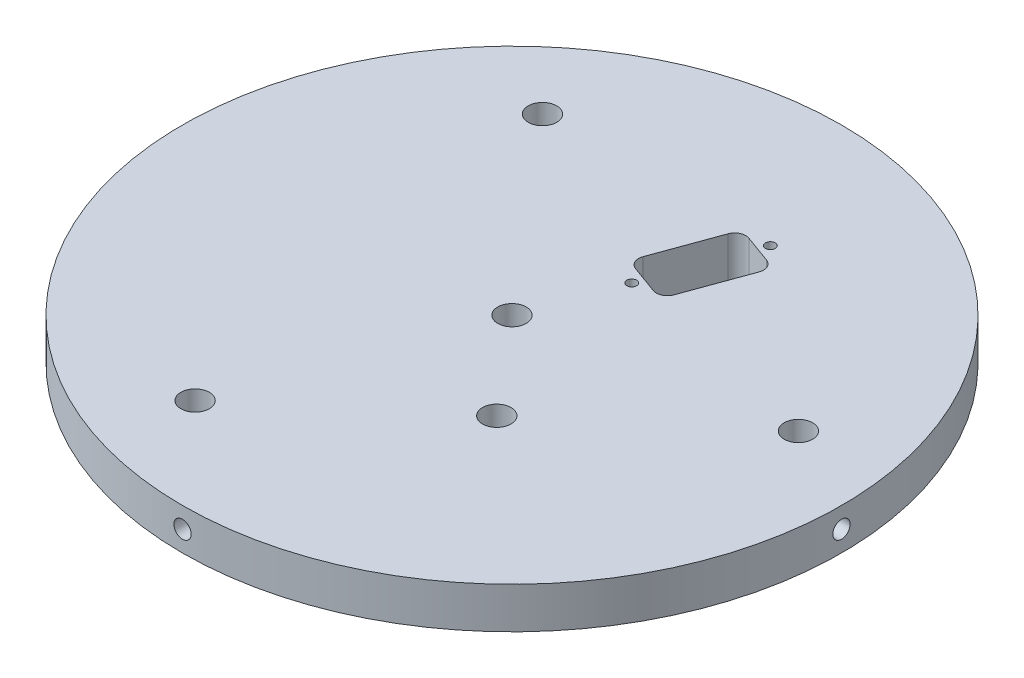
SolidWorks part; units mm, degrees
material "6061-T6 (SS)"
ref_plane "Front Plane" through (0, 0, 0) normal (0, 0, 1) x (1, 0, 0)
ref_plane "Top Plane" through (0, 0, 0) normal (0, 1, 0) x (1, 0, 0)
ref_plane "Right Plane" through (0, 0, 0) normal (1, 0, 0) x (0, 0, -1)
sketch "Sketch1" plane through (0, 0, 0) normal (0, 1, 0) x (1, 0, 0)
  line L0 (0, 0) -> (-50.3682, 60.0265)
  line L1 (0, 0) -> (50.3682, 60.0265)
  line L2 (0, 0) -> (0, 72.1431) construction
  circle A0 centre (0, 0) radius 78.359
  circle A1 centre (0, 0) radius 76.1746
  circle A2 centre (0, 0) radius 76.1746
  dimension "D1" = 156.718
  dimension "D2" = 152.3492
  dimension "D3" = 152.3492
  dimension "D4" = 80
extrude "Boss-Extrude1" add sketch "Sketch1" along normal blind 25.4 contours L2 A2 L1 A0 | L2 A1 L1 A2 | L2 A2 L1 A1 | L2 A0 L1 A2 | A2 L2 A1 L0 | A0 L2 A2 L0 | A2 L2 A0 L0 | A1 L2 A2 L0 region at (0, 0, 13.3592) region at (-23.5316, 0, -29.974) region at (-33.0764, 0, 70.9325) region at (-48.8794, 0, -59.85)
ref_plane "Plane1" through (0, 12.7, 0) normal (0, 1, 0) x (1, 0, 0)
sketch "Sketch6" plane through (0, 25.4, 0) normal (0, 1, 0) x (1, 0, 0)
  circle A0 centre (0, 0) radius 76.1746
  dimension "D1" = 152.3492
extrude "Boss-Extrude5" add sketch "Sketch6" along normal blind 9.525
sketch "Sketch7" plane through (0, 0, 0) normal (0, -1, 0) x (1, 0, 0)
  circle A0 centre (0, 0) radius 76.1746
  dimension "D1" = 152.3492
extrude "Boss-Extrude6" add sketch "Sketch7" along normal blind 9.525
sketch "Sketch8" plane through (0, -9.525, 0) normal (0, -1, 0) x (1, 0, 0)
  circle A0 centre (0, 0) radius 73.025
  dimension "D1" = 146.05
extrude "Cut-Extrude5" cut sketch "Sketch8" against normal up to surface (34.925 mm away) up to face at (0, 25.4, 76.1746)
ref_plane "Plane2" through (0, 0, -76.1746) normal (0, 0, -1) x (-1, 0, 0)
ref_plane "Plane5" through (0, 25.4, 0) normal (0, 1, 0) x (1, 0, 0)
ref_axis "Axis1" through (0, 0, 0) along (0, 1, 0)
sketch "Sketch3" plane through (0, 0, -76.1746) normal (0, 0, -1) x (-1, 0, 0)
  line L4 (76.1746, 0) -> (-76.1746, 0)
  line L5 (-76.1746, -9.525) -> (76.1746, -9.525)
  line L6 (76.1746, 25.4) -> (-76.1746, 25.4)
  line L7 (76.1746, 34.925) -> (-76.1746, 34.925)
  line L8 (0, 34.925) -> (0, 25.4) construction
  line L9 (0, 0) -> (0, -9.525) construction
  circle A0 centre (0, 30.1625) radius 2
  circle A1 centre (0, -4.7625) radius 2
  point P12 (0, 30.1625)
  point P13 (0, -4.7625)
  point P14 (-77.5445, 179.1871)
  dimension "D1" = 4
extrude "Cut-Extrude2" cut sketch "Sketch3" against normal blind 9.525 contours L8 A0 | L8 A0 | L9 A1 | L9 A1 region at (0, 30.1625, -76.1746) region at (0, -4.7625, -76.1746)
extrude "Cut-Extrude3" cut sketch "Sketch1<7>" against normal blind 9.525 from surface contours L2 A1 L1 A2 | A1 L2 A2 L0 | A2 L2 A0 L0 | L2 A2 L1 A0 region at (-23.5316, 0, -29.974) region at (-48.8794, 0, -59.85) starting at plane "Plane5"
sketch "Sketch1<7>" plane through (0, 0, 0) normal (0, 1, 0) x (1, 0, 0) same geometry as "Sketch1"
pattern_circular "CirPattern2" count 3 over 360 about axis through (0, 0, 0) along (0, 1, 0) of "Cut-Extrude3"
ref_plane "Plane3" through (0, 34.925, 0) normal (0, 1, 0) x (1, 0, 0)
sketch "Sketch4" plane through (0, 34.925, 0) normal (0, 1, 0) x (1, 0, 0)
  circle A0 centre (0, 0) radius 73.025
  dimension "D1" = 146.05
extrude "Boss-Extrude4" add sketch "Sketch4" against normal blind 9.525
pattern_circular "CirPattern3" count 4 over 360 about axis through (0, 0, 0) along (0, 1, 0) of "Cut-Extrude2"
sketch "Sketch9" plane through (0, 34.925, 0) normal (0, 1, 0) x (1, 0, 0)
  line L0 (0, 0) -> (-26.8004, -73.6334) construction
  line L1 (0, 0) -> (32.0596, -38.2071) construction
  circle A0 centre (0, 0) radius 3.3
  circle A1 centre (-19.5465, -53.7034) radius 3.3
  circle A2 centre (-36.7353, 43.7794) radius 3.3
  circle A3 centre (56.2818, 9.924) radius 3.3
  circle A4 centre (18.3677, -21.8897) radius 3.3
  point P9 (0, 0)
  point P10 (0, 0)
  point P15 (0, 0)
  dimension "D1" = 6.6
  dimension "D2" = 6.6
  dimension "D6" = 6.6
  dimension "D3" = 57.15
  dimension "D4" = 60
  dimension "D7" = 28.575
  dimension "D5" = 3
extrude "Cut-Extrude6" cut sketch "Sketch9" against normal through all
sketch "Sketch10" plane through (0, 25.4, 0) normal (0, 1, 0) x (1, 0, 0)
  circle A0 centre (0, 0) radius 82.3228
extrude "Cut-Extrude7" cut sketch "Sketch10" against normal through all
hole_wizard "Tap Drill for #4-40 Tap1" positions "Sketch12" profile "Sketch13" hole size "#4-40" standard "ANSI Inch" end condition through all
sketch "Sketch12" plane through (0, 34.925, 0) normal (0, 1, 0) x (1, 0, 0)
  line L0 (0, 0) -> (18.6243, 51.1699) construction
  line L2 (0, 0) -> (-36.7353, 43.7794) construction
  circle A0 centre (0, 0) radius 21.59 construction
  point P0 (7.3842, 20.288)
  point P2 (15.9347, 43.7803)
  dimension "D3" = 43.18
  dimension "D1" = 60
  dimension "D2" = 25
sketch "Sketch13" plane through (7.3842, 34.925, -20.288) normal (1, 0, 0) x (0, 0, 1)
  line L0 (0, 0) -> (0, 9.525)
  line L1 (0, 9.525) -> (1.1303, 9.525)
  line L2 (1.1303, 9.525) -> (1.1303, 0)
  line L5 (1.1303, 0) -> (0, 0)
  line L11 (0, -6.35) -> (0, 107.95) construction
  dimension "Thru Hole Dia." = 2.2606
  dimension "Thru Hole Depth" = 9.525
sketch "Sketch14" plane through (0, 34.925, 0) normal (0, 1, 0) x (1, 0, 0)
  line L0 (7.3842, 20.288) -> (15.9347, 43.7803) construction
  line L1 (14.6438, 22.7814) -> (19.8932, 37.2038)
  line L2 (11.3883, 21.2633) -> (4.9439, 23.6089)
  line L3 (18.3751, 40.4594) -> (11.9307, 42.8049)
  line L4 (3.4258, 26.8644) -> (8.6751, 41.2868)
  arc A0 (19.8932, 37.2038) -> (18.3751, 40.4594) centre (17.5063, 38.0725) ccw
  arc A1 (11.9307, 42.8049) -> (8.6751, 41.2868) centre (11.0619, 40.4181) ccw
  arc A2 (11.3883, 21.2633) -> (14.6438, 22.7814) centre (12.257, 23.6501) ccw
  arc A3 (4.9439, 23.6089) -> (3.4258, 26.8644) centre (5.8126, 25.9957) cw
  point P0 (8.1661, 22.4361)
  dimension "D4" = 2.54
  dimension "D5" = 2.54
  dimension "D1" = 2.286
  dimension "D2" = 2.286
  dimension "D3" = 11.938
extrude "Cut-Extrude9" cut sketch "Sketch14" against normal through all
equation "\"AB_Coupler_OD_Length\"= 1in"
equation "\"AB_Coupling_Section_Length\"= 0.375in"
equation "\"AB_Coupler_Length\"= \"AB_Coupler_OD_Length\" + \"AB_Coupling_Section_Length\" * 2"
equation "\"Cutout_Angle\" = 80"
equation "\"AB_Coupler_Num_Screws\"= 6"
equation "\"Num_Cutouts\" = 3"
equation "\"AB_Coupler_OD\"= 6.17in"
equation "\"AB_Coupler_ID\"= 5.75in"
equation "\"AB_Coupler_Surface_Diameter\"= 5.998in"
equation "\"D2@Sketch1\"=\"Bodytube_ID\""
equation "\"AB_Coupling_Screw_Diameter\"= 0.1065in"
equation "\"Aft_Section_Length\"= 39in"
equation "\"Aft_Lower_Length\"= 22in"
equation "\"Aft_Upper_Length\"= \"Aft_Section_Length\" - \"Aft_Lower_Length\" - \"AB_Coupler_OD_Length\""
equation "\"Mid_Coupler_Length\"= 13in"
equation "\"Lead_Screw_Dist\" = 2.25in"
equation "\"Lead_Screw_Diam\" = 11mm"
equation "\"Lead_Screw_Length\" = (\"Mid_Coupler_Length\" + 2*0.375in + 2*0.5in)"
equation "\"Bodytube_OD\" = 6.17in"
equation "\"Paddle_Pin_Offset\" = .25in"
equation "\"Bodytube_ID\" = 5.998in"
equation "\"Paddle_Pin_Radius\" = 2.25in"
equation "\"D1@Sketch4\"=\"AB_Coupler_ID\""
equation "\"D1@Sketch6\"=\"AB_Coupler_Surface_Diameter\""
equation "\"D1@Boss-Extrude5\"=\"AB_Coupling_Section_Length\""
equation "\"D1@Sketch7\"=\"AB_Coupler_Surface_Diameter\""
equation "\"D1@Boss-Extrude6\"=\"AB_Coupling_Section_Length\""
equation "\"D1@Sketch8\"=\"AB_Coupler_ID\""
equation "\"D3@Sketch9\"=\"Paddle_Pin_Radius\""
equation "\"Motor_OD\" = 4in"
equation "\"Fwd_Tube_Length\" = 40in"
equation "\"Mid_Tube_Length\" = 1in"
equation "\"AB_Paddle_Height\" = 0.375in"
equation "\"AB_Central_Bushing_Length\" = .75in"
equation "\"Paddle_Gear_OD\" = 3.2in"
equation "\"Fwd_BKHD_From_Top\" = 18in"
equation "\"Fin_Thickness\"= .118in"
equation "\"Guiderail_Cutout_Diameter\"= 1.5in"
equation "\"DB9_Hole_Dist\" = 25mm"
equation "\"D2@Sketch12\"=\"DB9_Hole_Dist\""
equation "\"Drive_Gear_OD\" = 1.7in"
equation "\"D3@Sketch12\"=\"Drive_Gear_OD\""
